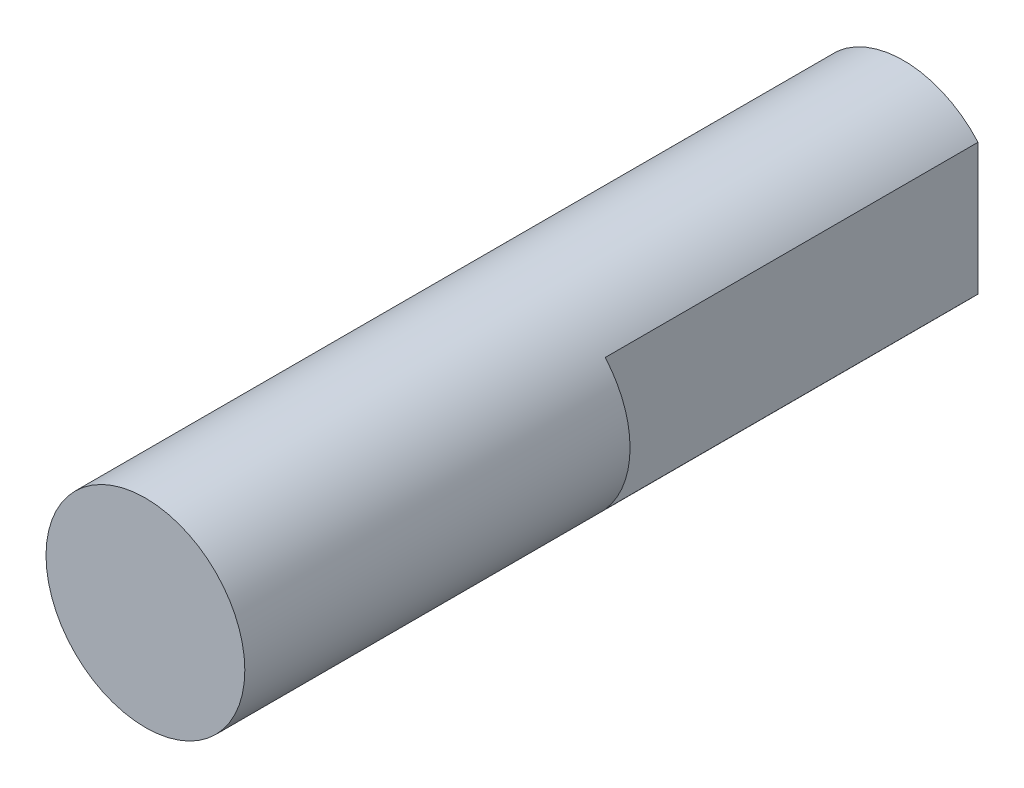
SolidWorks part; units mm, degrees
ref_plane "정면" through (0, 0, 0) normal (0, 0, 1) x (1, 0, 0)
ref_plane "윗면" through (0, 0, 0) normal (0, 1, 0) x (1, 0, 0)
ref_plane "우측면" through (0, 0, 0) normal (1, 0, 0) x (0, 0, -1)
sketch "스케치1" plane through (0, 0, 0) normal (0, 0, 1) x (1, 0, 0)
  circle A0 centre (0, 0) radius 4
  dimension "D1" = 8
extrude "보스-돌출1" add sketch "스케치1" along normal blind 10 and the other way blind 20.5
sketch "스케치3" plane through (0, 0, -20.5) normal (0, 0, -1) x (-1, 0, 0)
  line L0 (-3, 2.6458) -> (-3, -2.6458)
  line L1 (4, 0) -> (4, 8.1981) construction
  circle A0 centre (0, 0) radius 4 construction
  arc A1 (-3, 2.6458) -> (-3, -2.6458) centre (0, 0) ccw
  circle M3 centre (0, 0) radius 4
  dimension "D1" = 4
  dimension "D2" = 7
extrude "컷-돌출1" cut sketch "스케치3" against normal blind 15 contours L0 M3 region at (3.4046, 0, -20.5)
